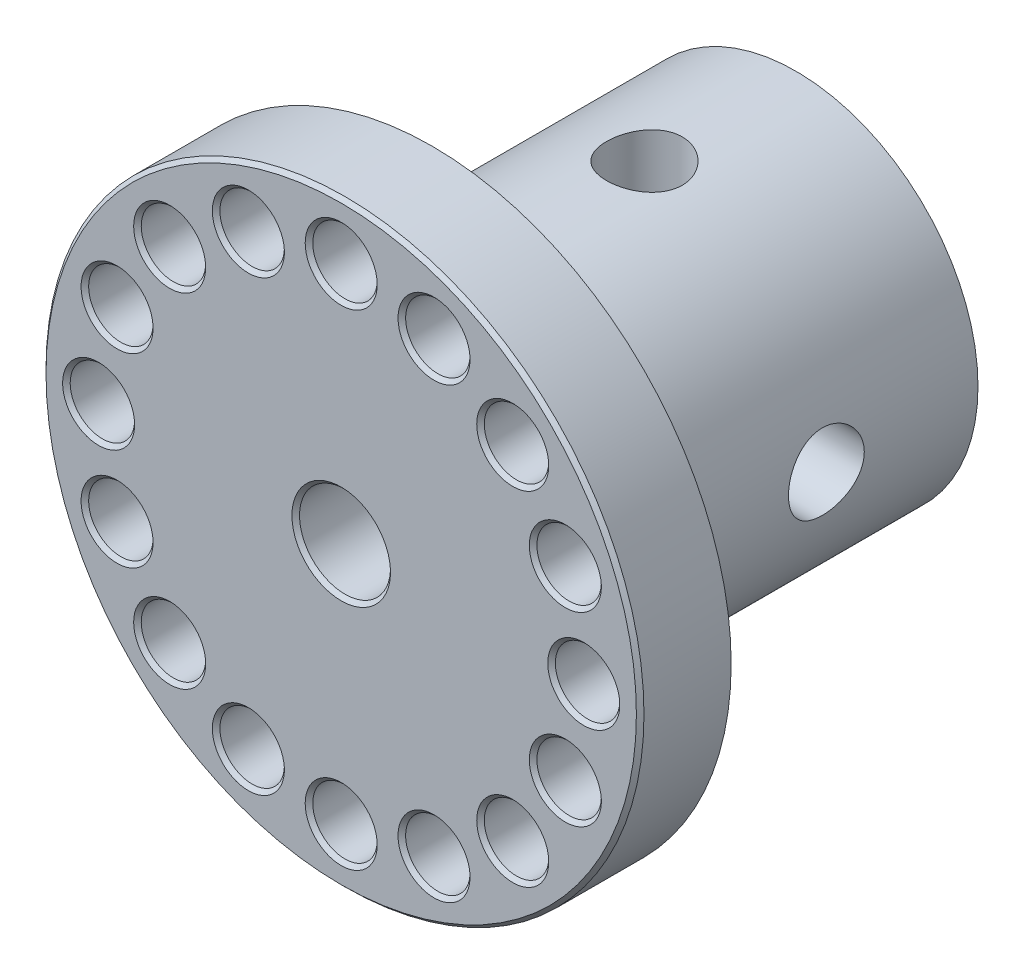
SolidWorks part; units mm, degrees
note: '?' marks a value the reader was unsure of.
ref_plane "Front" through (0, 0, 0) normal (0, 0, 1) x (1, 0, 0)
ref_plane "Top" through (0, 0, 0) normal (0, 1, 0) x (1, 0, 0)
ref_plane "Right" through (0, 0, 0) normal (1, 0, 0) x (0, 0, -1)
sketch "Sketch1" plane through (0, 0, 0) normal (1, 0, 0) x (0, 0, -1)
  line L0 (0, 31.3055) -> (0, 4.7625)
  line L1 (0, 31.3055) -> (9.525, 31.3055)
  line L2 (9.525, 31.3055) -> (9.525, 22.225)
  line L3 (12.7, 19.05) -> (47.625, 19.05)
  line L4 (47.625, 19.05) -> (47.625, 7.0231)
  line L5 (47.625, 7.0231) -> (15.875, 7.0231)
  line L6 (15.875, 7.0231) -> (15.875, 4.7625)
  line L7 (15.875, 4.7625) -> (0, 4.7625)
  line L8 (-8.5328, 0) -> (50.5372, 0) construction
  arc A0 (9.525, 22.225) -> (12.7, 19.05) centre (12.7, 22.225) ccw
  dimension "D1" = 3.175
  dimension "D2" = 9.525
  dimension "D3" = 47.625
  dimension "D4" = 9.525
  dimension "D5" = 14.0462
  dimension "D6" = 38.1
  dimension "D7" = 62.611
  dimension "D8" = 31.75
revolve "Base-Revolve" add sketch "Sketch1" angle 360 about L8
ref_axis "Axis1" through (0, 0, -41.4672) along (0, 0, 1)?
sketch "Sketch2" plane through (0, 0, 0) normal (0, 0, 1) x (1, 0, 0)
  circle A0 centre (0, 0) radius 25.4 construction
  circle A1 centre (25.4, 0) radius 3.3734
  dimension "D1" = 50.8
  dimension "D2" = 6.7469
extrude "Cut-Extrude1" cut sketch "Sketch2" against normal through all
pattern_circular "CirPattern1" count 16 every 22.5 about axis through (0, 0, 0) along (0, 0, 1) of "Cut-Extrude1"
sketch "Sketch4" plane through (0, 0, 0) normal (0, 1, 0) x (1, 0, 0)
  line L0 (0, 9.525) -> (0, 0) construction
  line L2 (4.7625, 15.875) -> (-4.7625, 15.875) construction
  line L3 (19.05, 47.625) -> (-19.05, 47.625) construction
  circle A0 centre (0, 15.875) radius 2.3813
  dimension "D1" = 4.7625
  dimension "D2" = 31.75
extrude "Cut-Extrude2" cut sketch "Sketch4" along normal through all
sketch "Sketch3" plane through (0, 0, -47.625) normal (0, 0, -1) x (-1, 0, 0)
  line L0 (-2.54, 9.3599) -> (2.54, 9.3599)
  line L1 (-2.54, 9.3599) -> (-2.54, 6.5477)
  line L2 (2.54, 9.3599) -> (2.54, 6.5477)
  line L3 (0, 0) -> (0, 9.3599) construction
  circle A0 centre (0, 0) radius 7.0231 construction
  arc A1 (2.54, 6.5477) -> (-2.54, 6.5477) centre (0, 0) ccw
  circle A2 centre (0, 0) radius 7.0231 construction
  dimension "D1" = 16.383
  dimension "D2" = 5.08
extrude "Cut-Extrude3" cut sketch "Sketch3" against normal up to surface (31.75 mm away)
sketch "Sketch5" plane through (0, 0, 0) normal (0, 1, 0) x (1, 0, 0)
  line L0 (0, 9.525) -> (0, 0) construction
  line L1 (19.05, 47.625) -> (-19.05, 47.625) construction
  circle A0 centre (0, 31.75) radius 3.9688
  dimension "D1" = 7.9375
  dimension "D2" = 15.875
extrude "Cut-Extrude4" cut sketch "Sketch5" along normal through all
pattern_circular "CirPattern2" count 2 every 90 about axis through (0, 0, -41.4672) along (0, 0, 1) of "Cut-Extrude4"
chamfer "Chamfer1" distance 0.3969 angle 45 18 edges at (11.0111, -26.5832, 0) (31.3055, 0, 0) (20.3459, -20.3459, 0) (26.5832, -11.0111, 0) (28.7734, 0, 0) (26.5832, 11.0111, 0) (20.3459, 20.3459, 0) (11.0111, 26.5832, 0) (0, 28.7734, 0) (-11.0111, 26.5832, 0) (-20.3459, 20.3459, 0) (-26.5832, 11.0111, 0) (-28.7734, 0, 0) (-26.5832, -11.0111, 0) (-20.3459, -20.3459, 0) (-11.0111, -26.5832, 0) (0, -28.7734, 0) (4.7625, 0, 0)
